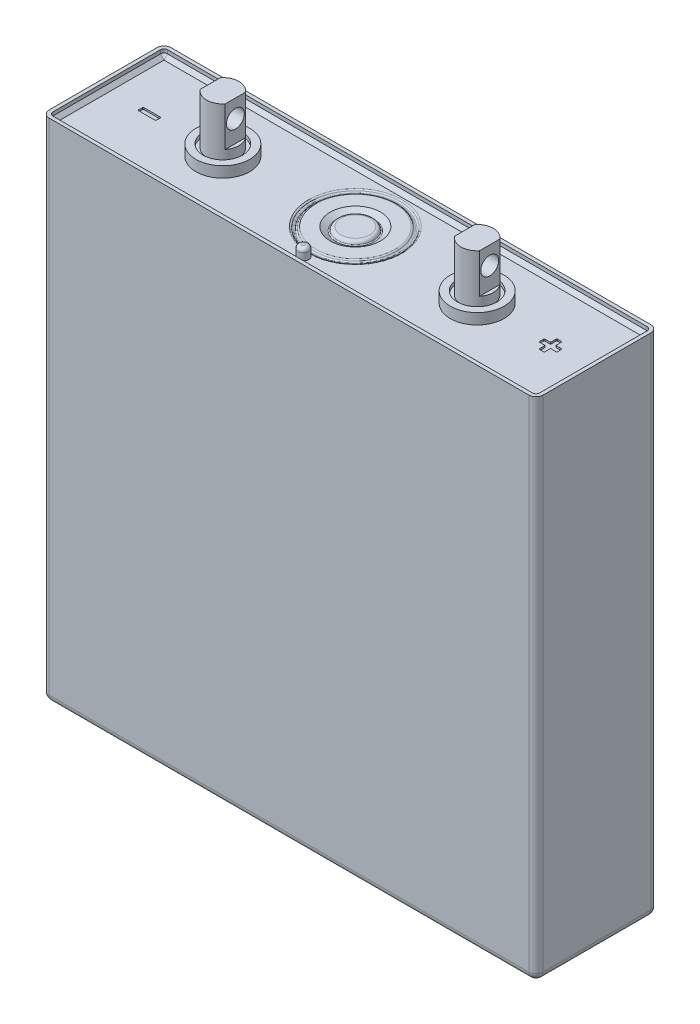
SolidWorks part; units mm, degrees
material "201 Annealed Stainless Steel (SS)"
ref_plane "Front Plane" through (0, 0, 0) normal (0, 0, 1) x (1, 0, 0)
ref_plane "Top Plane" through (0, 0, 0) normal (0, 1, 0) x (1, 0, 0)
ref_plane "Right Plane" through (0, 0, 0) normal (1, 0, 0) x (0, 0, -1)
sketch "Sketch1" plane through (0, 0, 0) normal (0, 1, 0) x (1, 0, 0)
  line L1 (68.85, -17) -> (-68.85, -17)
  line L2 (68.85, -17) -> (68.85, 17)
  line L3 (68.85, 17) -> (-68.85, 17)
  line L4 (-68.85, -17) -> (-68.85, 17)
  line L5 (68.85, -17) -> (-68.85, 17) construction
  line L6 (68.85, 17) -> (-68.85, -17) construction
  point P0 (0, 0)
  dimension "D1" = 34
  dimension "D2" = 137.7
extrude "Boss-Extrude1" add sketch "Sketch1" along normal blind 141.3
fillet "Fillet1" radius 2 8 edges at (0, 0, -17) (-68.85, 0, 0) (68.85, 0, 0) (0, 0, 17) (68.85, 70.65, 17) (68.85, 70.65, -17) (-68.85, 70.65, -17) (-68.85, 70.65, 17)
sketch "Sketch2" plane through (0, 141.3, 0) normal (0, 1, 0) x (1, 0, 0)
  line L8 (-66.85, -16) -> (66.85, -16)
  line L9 (67.85, -15) -> (67.85, 15)
  line L10 (66.85, 16) -> (-66.85, 16)
  line L11 (-67.85, 15) -> (-67.85, -15)
  line L12 (-66.85, -16) -> (66.85, -16)
  line L13 (67.85, -15) -> (67.85, 15)
  line L14 (66.85, 16) -> (-66.85, 16)
  line L15 (-67.85, 15) -> (-67.85, -15)
  arc A8 (66.85, -16) -> (67.85, -15) centre (66.85, -15) ccw
  arc A9 (67.85, 15) -> (66.85, 16) centre (66.85, 15) ccw
  arc A10 (-66.85, 16) -> (-67.85, 15) centre (-66.85, 15) ccw
  arc A11 (-67.85, -15) -> (-66.85, -16) centre (-66.85, -15) ccw
  arc A12 (66.85, -16) -> (67.85, -15) centre (66.85, -15) ccw
  arc A13 (67.85, 15) -> (66.85, 16) centre (66.85, 15) ccw
  arc A14 (-66.85, 16) -> (-67.85, 15) centre (-66.85, 15) ccw
  arc A15 (-67.85, -15) -> (-66.85, -16) centre (-66.85, -15) ccw
  dimension "D1" = 1
extrude "Cut-Extrude1" cut sketch "Sketch2" against normal blind 2
chamfer "Chamfer1" distance 1 angle 45 8 edges at (-67.85, 139.3, 0) (-67.5571, 139.3, -15.7071) (0, 139.3, -16) (67.5571, 139.3, -15.7071) (67.85, 139.3, 0) (67.5571, 139.3, 15.7071) (0, 139.3, 16) (-67.5571, 139.3, 15.7071)
sketch "Sketch3" plane through (0, 139.3, 0) normal (0, 1, 0) x (1, 0, 0)
  line L0 (0, 17) -> (0, -17) construction
  line L1 (66.85, 17) -> (-66.85, 17) construction
  line L2 (-66.85, -17) -> (66.85, -17) construction
  line L3 (-35.45, 17) -> (-35.45, -17) construction
  line L4 (35.45, 17) -> (35.45, -17) construction
  line L5 (-35.45, 0) -> (0, 0) construction
  line L6 (0, 0) -> (35.45, 0) construction
  line L7 (-35.45, 0) -> (-68.85, 0) construction
  line L8 (-68.85, 15) -> (-68.85, -15) construction
  line L9 (35.45, 0) -> (68.85, 0) construction
  line L10 (68.85, -15) -> (68.85, 15) construction
  line L11 (-52.15, 0) -> (-52.15, 17) construction
  line L12 (52.15, 0) -> (52.15, 17) construction
  line L13 (-52.15, 8.5) -> (52.15, 8.5) construction
  circle A0 centre (-35.45, 0) radius 7.5
  circle A1 centre (35.45, 0) radius 7.5
  dimension "D2" = 15
  dimension "D1" = 70.9
extrude "Boss-Extrude2" add sketch "Sketch3" along normal blind 3
sketch "Sketch4" plane through (0, 142.3, 0) normal (0, 1, 0) x (1, 0, 0)
  circle A0 centre (35.45, 0) radius 7.5 construction
  circle A1 centre (-35.45, 0) radius 7.5 construction
  circle A2 centre (35.45, 0) radius 7.5 construction
  circle A3 centre (-35.45, 0) radius 7.5 construction
  circle A4 centre (-35.45, 0) radius 5.5
  circle A5 centre (35.45, 0) radius 5.5
  dimension "D1" = 2
extrude "Cut-Extrude2" cut sketch "Sketch4" against normal blind 1
sketch "Sketch5" plane through (0, 141.3, 0) normal (0, 1, 0) x (1, 0, 0)
  circle A0 centre (-35.45, 0) radius 4.5
  circle A1 centre (-35.45, 0) radius 5.5
  circle A2 centre (-35.45, 0) radius 5.5 construction
  dimension "D2" = 9
  dimension "D1" = 0
extrude "Boss-Extrude3" add sketch "Sketch5" along normal blind 13.8
sketch "Sketch6" plane through (0, 0, 0) normal (0, 0, 1) x (1, 0, 0)
  line L0 (-35.45, 155.1) -> (-35.45, 142.3) construction
  line L1 (-30.95, 155.1) -> (-39.95, 155.1) construction
  line L2 (-27.95, 142.3) -> (-42.95, 142.3) construction
  line L4 (-30.95, 155.1) -> (-31.95, 155.1)
  line L5 (-30.95, 155.1) -> (-30.95, 144.1)
  line L6 (-30.95, 144.1) -> (-31.95, 144.1)
  line L7 (-31.95, 155.1) -> (-31.95, 144.1)
  line L8 (-39.95, 155.1) -> (-38.95, 155.1)
  line L9 (-39.95, 155.1) -> (-39.95, 144.1)
  line L10 (-39.95, 144.1) -> (-38.95, 144.1)
  line L11 (-38.95, 155.1) -> (-38.95, 144.1)
  dimension "D1" = 1
  dimension "D2" = 11
extrude "Cut-Extrude3" cut sketch "Sketch6" against normal through all both and the other way through all
sketch "Sketch7" plane through (-31.95, 0, 0) normal (1, 0, 0) x (0, 0, -1)
  line L0 (0, 155.1) -> (0, 142.3) construction
  line L1 (2.8284, 155.1) -> (-2.8284, 155.1) construction
  line L2 (7.5, 142.3) -> (-7.5, 142.3) construction
  circle A0 centre (0, 150.1) radius 2.5
  dimension "D1" = 5
  dimension "D2" = 5
extrude "Cut-Extrude4" cut sketch "Sketch7" against normal blind 13.8
mirror "Mirror1" about plane through (0, 0, 0) normal (1, 0, 0) of "Boss-Extrude3", "Cut-Extrude3", "Cut-Extrude4"
sketch "Sketch8" plane through (0, 139.3, 0) normal (0, 1, 0) x (1, 0, 0)
  line L0 (-42.95, 0) -> (42.95, 0) construction
  line L3 (0, -17) -> (0, 17) construction
  line L4 (-66.85, -17) -> (66.85, -17) construction
  line L5 (66.85, 17) -> (-66.85, 17) construction
  line L6 (-42.95, -17) -> (-42.95, 17) construction
  line L7 (42.95, -17) -> (42.95, 17) construction
  line L8 (-42.95, 0) -> (-68.85, 0) construction
  line L9 (-68.85, 15) -> (-68.85, -15) construction
  line L10 (42.95, 0) -> (68.85, 0) construction
  line L11 (68.85, -15) -> (68.85, 15) construction
  line L13 (-53.65, -0.75) -> (-58.15, -0.75)
  line L14 (-53.4, -0.5) -> (-53.4, 0.5)
  line L15 (-53.65, 0.75) -> (-58.15, 0.75)
  line L16 (-58.4, -0.5) -> (-58.4, 0.5)
  line L17 (-53.4, -0.75) -> (-58.4, 0.75) construction
  line L18 (-53.4, 0.75) -> (-58.4, -0.75) construction
  line L19 (58.15, -0.75) -> (53.65, -0.75)
  line L20 (58.4, -0.5) -> (58.4, 0.5)
  line L21 (58.15, 0.75) -> (53.65, 0.75)
  line L22 (53.4, -0.5) -> (53.4, 0.5)
  line L23 (58.4, -0.75) -> (53.4, 0.75) construction
  line L24 (58.4, 0.75) -> (53.4, -0.75) construction
  line L25 (56.4, -2.5) -> (55.4, -2.5)
  line L26 (56.65, -2.25) -> (56.65, 2.25)
  line L27 (56.4, 2.5) -> (55.4, 2.5)
  line L28 (55.15, -2.25) -> (55.15, 2.25)
  line L29 (56.65, -2.5) -> (55.15, 2.5) construction
  line L30 (56.65, 2.5) -> (55.15, -2.5) construction
  circle A0 centre (-35.45, 0) radius 7.5 construction
  circle A1 centre (35.45, 0) radius 7.5 construction
  arc A2 (-53.65, -0.75) -> (-53.4, -0.5) centre (-53.65, -0.5) ccw
  arc A3 (-53.4, 0.5) -> (-53.65, 0.75) centre (-53.65, 0.5) ccw
  arc A4 (-58.15, -0.75) -> (-58.4, -0.5) centre (-58.15, -0.5) cw
  arc A5 (-58.15, 0.75) -> (-58.4, 0.5) centre (-58.15, 0.5) ccw
  arc A6 (56.4, -2.5) -> (56.65, -2.25) centre (56.4, -2.25) ccw
  arc A7 (55.4, -2.5) -> (55.15, -2.25) centre (55.4, -2.25) cw
  arc A8 (58.15, -0.75) -> (58.4, -0.5) centre (58.15, -0.5) ccw
  arc A9 (58.4, 0.5) -> (58.15, 0.75) centre (58.15, 0.5) ccw
  arc A10 (53.65, -0.75) -> (53.4, -0.5) centre (53.65, -0.5) cw
  arc A11 (53.65, 0.75) -> (53.4, 0.5) centre (53.65, 0.5) ccw
  arc A12 (55.4, 2.5) -> (55.15, 2.25) centre (55.4, 2.25) ccw
  arc A13 (56.65, 2.25) -> (56.4, 2.5) centre (56.4, 2.25) ccw
  point P1 (-55.9, 0)
  point P28 (55.9, 0)
  point P33 (55.9, 0)
  dimension "D3" = 0.25
  dimension "D1" = 5
  dimension "D2" = 1.5
extrude "Cut-Extrude5" cut sketch "Sketch8" against normal blind 0.5 contours L26 A13 L27 A12 L28 L21 | L28 L19 L26 L21 | L21 A11 L22 A10 L19 L28 | L20 A9 L21 L26 L19 A8 | A7 L25 A6 L26 L19 L28 | L15 A5 L16 A4 L13 A2 L14 A3 region at (-55.9, 139.3, 0) region at (57.5165, 139.3, 0) region at (55.9, 139.3, 1.6165) region at (55.9, 139.3, 0) region at (54.2835, 139.3, 0) region at (55.9, 139.3, -1.6165)
sketch "Sketch9" plane through (0, 139.3, 0) normal (0, 1, 0) x (1, 0, 0)
  line L0 (0, 17) -> (0, -17) construction
  line L1 (66.85, 17) -> (-66.85, 17) construction
  line L2 (-66.85, -17) -> (66.85, -17) construction
  circle A0 centre (0, 1.5) radius 12.5
  circle A1 centre (0, 1.5) radius 11.5
  point P9 (0, 0)
  dimension "D1" = 25
  dimension "D2" = 1
  dimension "D3" = 1.5
extrude "Cut-Extrude6" cut sketch "Sketch9" against normal blind 0.5
sketch "Sketch10" plane through (0, 139.3, 0) normal (0, 1, 0) x (1, 0, 0)
  line L0 (0, 17) -> (0, -17) construction
  line L1 (66.85, 17) -> (-66.85, 17) construction
  line L2 (-66.85, -17) -> (66.85, -17) construction
  line L3 (-66.85, -15) -> (66.85, -15) construction
  circle A0 centre (0, -13) radius 1.5
  dimension "D1" = 3
  dimension "D2" = 2
extrude "Boss-Extrude4" add sketch "Sketch10" along normal blind 3
fillet "Fillet2" radius 1 1 edges at (0, 142.3, 14.5)
ref_plane "Plane1" through (0, 0, -1.5) normal (0, 0, 1) x (1, 0, 0)
sketch "Sketch12" plane through (0, 0, -1.5) normal (0, 0, 1) x (1, 0, 0)
  line L0 (0, 0) -> (0, 163.2499) construction
  line L1 (11.5, 139.3) -> (-11.5, 139.3) construction
  line L2 (11.5, 139.3) -> (-11.5, 139.3) construction
  line L3 (-5.3778, 138.3351) -> (-7, 139.3)
  line L4 (-5, 138.55) -> (-5, 139.3)
  line L5 (-5, 139.3) -> (-7, 139.3)
  line L6 (-5, 139.3) -> (-5, 140.1136)
  line L7 (-5, 140.1136) -> (-7, 140.1136)
  line L8 (-7, 140.1136) -> (-7, 139.3)
  arc A1 (-5, 138.55) -> (-5.3778, 138.3351) centre (-5.25, 138.55) cw
  dimension "D2" = 0.25
  dimension "D1" = 0.75
  dimension "D3" = 2
  dimension "D4" = 5
revolve "Cut-Revolve1" cut sketch "Sketch12" angle 360 about L0 region at (-5.6887, 138.9277, -1.5) region at (-6, 139.7068, -1.5)
fillet "Fillet3" radius 1 1 edges at (0, 139.3, 3.5)
fillet "Fillet4" radius 0.5 2 edges at (0, 139.3, 10) (0, 139.3, 11)
fillet "Fillet5" radius 0.5 2 edges at (0, 138.8, 11) (0, 138.8, 10)
equation "\"Width\"= 137.7mm"
equation "\"Depth\"= 34mm"
equation "\"Height\"= 141.3mm"
equation "\"Height_to_Leads\"= 155.1mm"
equation "\"Distance_Between_Leads\"= 70.9mm"
equation "\"D1@Sketch1\"=\"Depth\""
equation "\"D2@Sketch1\"=\"Width\""
equation "\"D1@Boss-Extrude1\"=\"Height\""
equation "\"D1@Sketch3\"=\"Distance_Between_Leads\""
equation "\"D1@Boss-Extrude3\"=\"Height_to_Leads\"-\"Height\""
